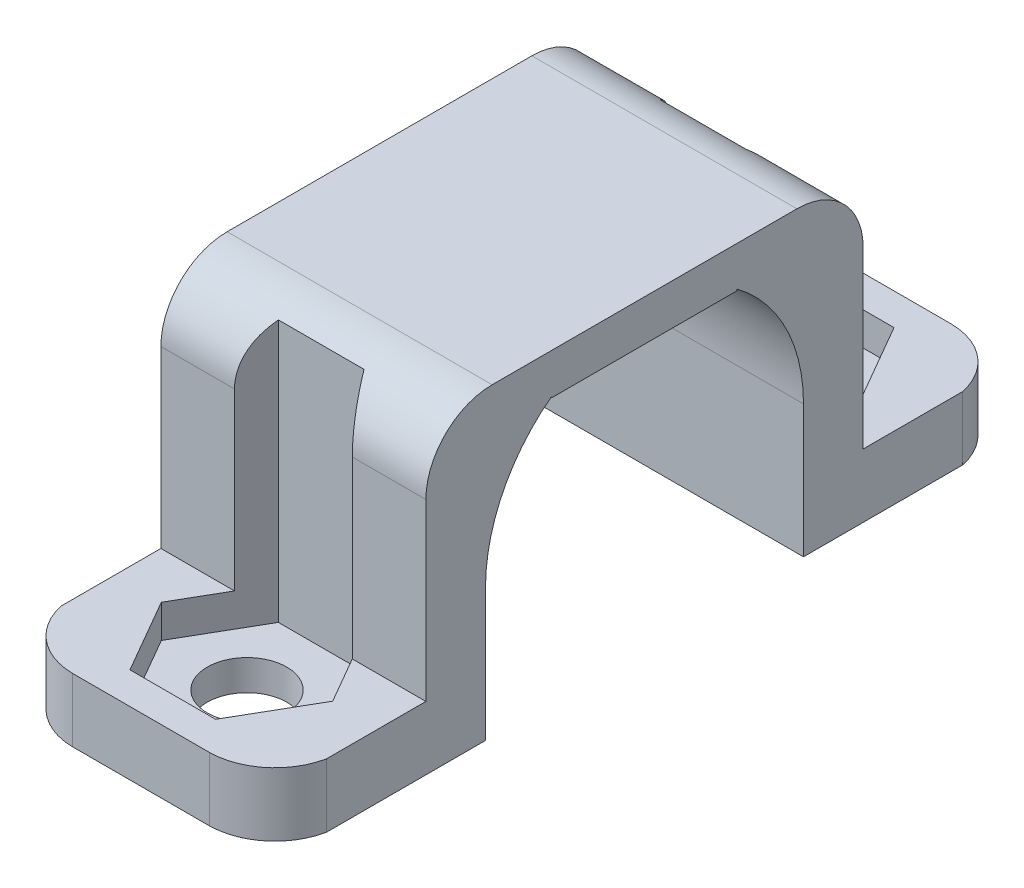
SolidWorks part; units mm, degrees
ref_plane "Front Plane" through (0, 0, 0) normal (0, 0, 1) x (1, 0, 0)
ref_plane "Top Plane" through (0, 0, 0) normal (0, 1, 0) x (1, 0, 0)
ref_plane "Right Plane" through (0, 0, 0) normal (1, 0, 0) x (0, 0, -1)
sketch "Sketch1" plane through (0, 0, 0) normal (1, 0, 0) x (0, 0, -1)
  line L0 (0.3355, 3.0184) -> (0.3355, -6.9816) construction
  line L1 (-5.6645, 3.0184) -> (6.3355, 3.0184)
  line L2 (-5.6645, 3.0184) -> (-5.6645, -6.9816)
  line L3 (-5.6645, -6.9816) -> (6.3355, -6.9816)
  line L4 (6.3355, 3.0184) -> (6.3355, -6.9816)
  line L5 (-5.6645, -1.9816) -> (6.3355, -1.9816) construction
  line L7 (3.8355, 3.0184) -> (3.8355, -6.9816)
  line L8 (-3.1645, 3.0184) -> (-3.1645, -6.9816)
  line L9 (-5.6645, 3.0184) -> (-7.9145, 3.0184)
  line L10 (-5.6645, 3.0184) -> (-5.6645, -6.9816)
  line L11 (-5.6645, -6.9816) -> (-7.9145, -6.9816)
  line L12 (-7.9145, 3.0184) -> (-7.9145, -6.9816)
  line L13 (-7.9145, -6.9816) -> (-13.6645, -6.9816)
  line L14 (-7.9145, -6.9816) -> (-7.9145, -4.5816)
  line L15 (-7.9145, -4.5816) -> (-13.6645, -4.5816)
  line L16 (-13.6645, -6.9816) -> (-13.6645, -4.5816)
  line L17 (-7.9145, 3.0184) -> (6.3355, 3.0184)
  line L18 (-7.9145, 3.0184) -> (-7.9145, 4.5184)
  line L19 (-7.9145, 4.5184) -> (6.3355, 4.5184)
  line L20 (6.3355, 3.0184) -> (6.3355, 4.5184)
  line L21 (6.3355, 4.5184) -> (8.5855, 4.5184)
  line L22 (6.3355, 4.5184) -> (6.3355, -6.9816)
  line L23 (6.3355, -6.9816) -> (8.5855, -6.9816)
  line L24 (8.5855, 4.5184) -> (8.5855, -6.9816)
  line L25 (8.5855, -6.9816) -> (14.3355, -6.9816)
  line L26 (8.5855, -6.9816) -> (8.5855, -4.5816)
  line L27 (8.5855, -4.5816) -> (14.3355, -4.5816)
  line L28 (14.3355, -6.9816) -> (14.3355, -4.5816)
  line L29 (-3.1645, 3.0184) -> (3.8355, 3.0184)
  line L30 (-3.1645, 3.0184) -> (-3.1645, 2.9684)
  line L31 (-3.1645, 2.9684) -> (3.8355, 2.9684)
  line L32 (3.8355, 3.0184) -> (3.8355, 2.9684)
  arc A1 (-3.1645, -6.9816) -> (-3.1645, 3.0184) centre (0.5855, -1.9816) cw
  arc A2 (3.8355, 3.0184) -> (3.8355, -6.9816) centre (0.0855, -1.9816) cw
  arc A5 (-5.4145, 4.5184) -> (-7.9145, 2.0184) centre (-5.4145, 2.0184) ccw
  arc A6 (6.0855, 4.5184) -> (8.5855, 2.0184) centre (6.0855, 2.0184) cw
  dimension "D1" = 12
  dimension "D2" = 10
  dimension "D3" = 3.5
  dimension "D4" = 7
  dimension "D5" = 2.5
  dimension "D6" = 5.75
  dimension "D7" = 2.4
  dimension "D8" = 1.5
  dimension "D9" = 2.5
  dimension "D10" = 5.75
  dimension "D11" = 2.4
  dimension "D12" = 0.05
  dimension "D13" = 2.5
  dimension "D14" = 28
  dimension "D15" = 14
extrude "Boss-Extrude1" add sketch "Sketch1" along normal blind 10 region at (0, 3.7522, 0.3758) region at (0, 1.8239, 4.9498) region at (0, -1.9961, 6.7863) region at (0, 1.8239, -5.6207) region at (0, -1.5151, -7.4294) region at (0, -5.7816, 10.7895) region at (0, -5.7816, -11.4605)
sketch "Sketch2" plane through (0, -4.5816, 0) normal (0, 1, 0) x (1, 0, 0)
  line L0 (5, -13.6645) -> (5, 14.3355) construction
  line L1 (10, -13.6645) -> (0, -13.6645) construction
  line L2 (10, 14.3355) -> (0, 14.3355) construction
  line L4 (8.2332, 10.3355) -> (6.6166, 13.1355)
  line L5 (6.6166, 13.1355) -> (3.3834, 13.1355)
  line L6 (3.3834, 13.1355) -> (1.7668, 10.3355)
  line L7 (1.7668, 10.3355) -> (3.3834, 7.5355)
  line L8 (3.3834, 7.5355) -> (6.6166, 7.5355)
  line L9 (6.6166, 7.5355) -> (8.2332, 10.3355)
  line L10 (8.2332, -9.6645) -> (6.6166, -6.8645)
  line L11 (6.6166, -6.8645) -> (3.3834, -6.8645)
  line L12 (3.3834, -6.8645) -> (1.7668, -9.6645)
  line L13 (1.7668, -9.6645) -> (3.3834, -12.4645)
  line L14 (3.3834, -12.4645) -> (6.6166, -12.4645)
  line L15 (6.6166, -12.4645) -> (8.2332, -9.6645)
  circle A0 centre (5, 10.3355) radius 2.8 construction
  circle A1 centre (5, -9.6645) radius 2.8 construction
  circle A2 centre (5, 10.3355) radius 1.5
  circle A3 centre (5, -9.6645) radius 1.5
  point P6 (5, 10.3355)
  point P8 (5, -9.6645)
  dimension "D5" = 3
  dimension "D1" = 20
  dimension "D2" = 4
  dimension "D4" = 5.6
extrude "Cut-Extrude1" cut sketch "Sketch2" against normal blind 1.25 and the other way blind 25 contours A2 | L4 L5 L6 L7 L8 L9 | A3 | L10 L11 L12 L13 L14 L15
sketch "Sketch6" plane through (0, -4.5816, 0) normal (0, 1, 0) x (1, 0, 0)
  line L0 (5, 14.3355) -> (5, -13.6645) construction
  line L1 (0, 14.3355) -> (2.4872, 14.3355)
  line L2 (0, 14.3355) -> (0, 11.3326)
  line L5 (10, 14.3355) -> (0, 14.3355) construction
  line L6 (10, -13.6645) -> (0, -13.6645) construction
  line L7 (4.0427, -10.8194) -> (3.65, -10.3185) construction
  line L8 (10, 0.3355) -> (0, 0.3355) construction
  line L9 (10, -5.4145) -> (10, 6.0855) construction
  line L10 (0, -5.4145) -> (0, 6.0855) construction
  line L12 (0, 14.3355) -> (10, 14.3355)
  line L13 (0, 14.3355) -> (0, -13.6645)
  line L14 (0, -13.6645) -> (10, -13.6645)
  line L15 (10, 14.3355) -> (10, -13.6645)
  circle A0 centre (5, 10.3355) radius 1.5
  circle A1 centre (5, -9.6645) radius 1.5
  arc A2 (0, 11.3326) -> (2.5359, 14.3342) centre (2.4488, 11.8358) cw
  arc A3 (10, 11.3326) -> (7.4641, 14.3342) centre (7.5512, 11.8358) ccw
  arc A4 (10, -10.6617) -> (7.4641, -13.6633) centre (7.5512, -11.1648) cw
  arc A5 (0, -10.6617) -> (2.5359, -13.6633) centre (2.4488, -11.1648) ccw
  circle M1 centre (5, 10.3355) radius 1.5
  dimension "D1" = 2.5
  dimension "D3" = 3
  dimension "D4" = 3
  dimension "D2" = 2.5
extrude "Cut-Extrude2" cut sketch "Sketch6" against normal blind 20 contours M1 | L2 A2 L1 | A3 L15 L12 | A5 L13 L14 | A1 | L15 A4 L14 region at (0.5549, -4.5816, -13.8244) region at (9.4451, -4.5816, -13.8244) region at (0.5549, -4.5816, 13.1535) region at (9.4451, -4.5816, 13.1535) region at (5, -4.5816, -10.3355) region at (5, -4.5816, 9.6645)
